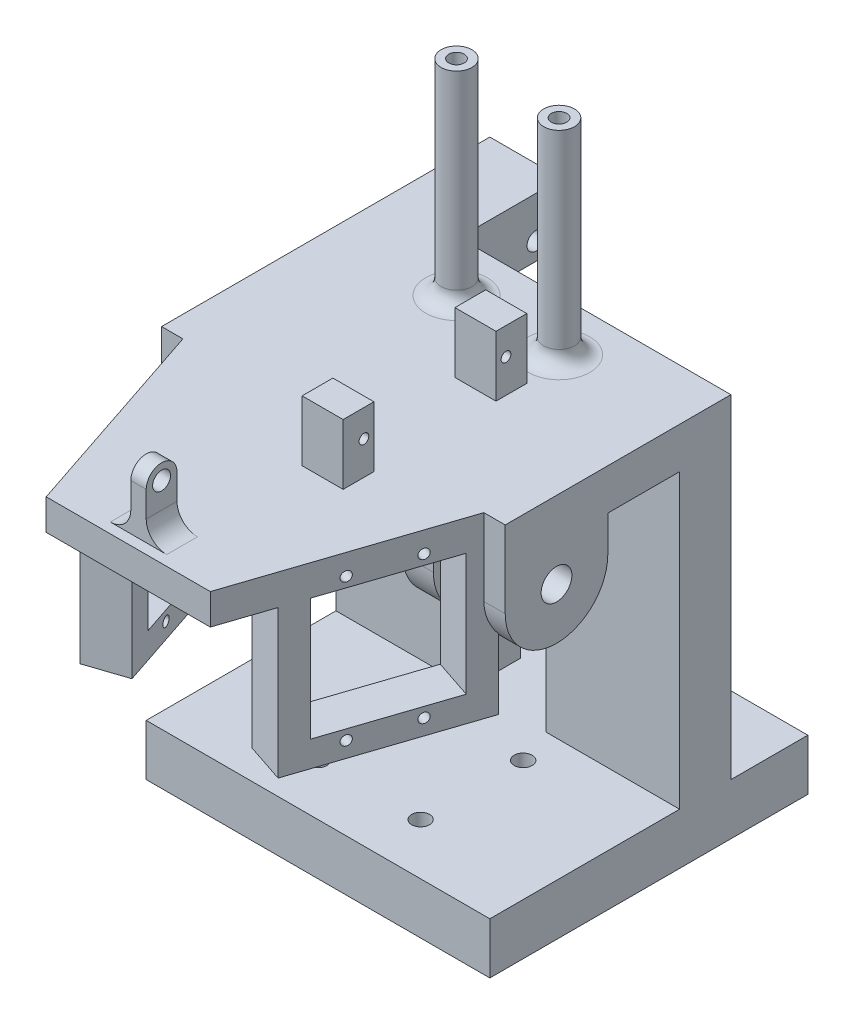
SolidWorks part; units mm, degrees
ref_plane "前视基准面" through (0, 0, 0) normal (0, 0, 1) x (1, 0, 0)
ref_plane "上视基准面" through (0, 0, 0) normal (0, 1, 0) x (1, 0, 0)
ref_plane "右视基准面" through (0, 0, 0) normal (1, 0, 0) x (0, 0, -1)
sketch "草图1" plane through (0, 0, 0) normal (0, 1, 0) x (1, 0, 0)
  line L1 (-33.5, 31) -> (33.5, 31)
  line L2 (-33.5, 31) -> (-33.5, -31)
  line L3 (-33.5, -31) -> (33.5, -31)
  line L4 (33.5, 31) -> (33.5, -31)
  line L5 (-33.5, 31) -> (33.5, -31) construction
  line L6 (-33.5, -31) -> (33.5, 31) construction
  point P0 (0, 0)
  dimension "D1" = 62
  dimension "D2" = 67
extrude "凸台-拉伸1" add sketch "草图1" along normal blind 10
sketch "草图3" plane through (0, 10, 0) normal (0, 1, 0) x (1, 0, 0)
  line L0 (-33.5, 31) -> (-33.5, -31) construction
  line L1 (-33.5, 36) -> (-19.5, 36)
  line L2 (-33.5, 36) -> (-33.5, 16)
  line L3 (-33.5, 16) -> (-19.5, 16)
  line L4 (-19.5, 36) -> (-19.5, 16)
  line L5 (33.5, 31) -> (-33.5, 31) construction
  dimension "D1" = 20
  dimension "D2" = 5
  dimension "D3" = 19.5
extrude "凸台-拉伸2" add sketch "草图3" along normal blind 12.5
sketch "草图4" plane through (-33.5, 0, 0) normal (-1, 0, 0) x (0, 0, 1)
  line L1 (-16, 10) -> (-6, 10)
  line L2 (-16, 10) -> (-16, 75)
  line L3 (-16, 75) -> (-6, 75)
  line L4 (-6, 10) -> (-6, 75)
  dimension "D1" = 10
  dimension "D2" = 65
extrude "凸台-拉伸3" add sketch "草图4" against normal blind 67
sketch "草图5" plane through (0, 75, 0) normal (0, 1, 0) x (1, 0, 0)
  line L0 (33.5, -31) -> (33.5, 6) construction
  line L1 (-33.5, 16) -> (33.5, 16)
  line L2 (-33.5, 16) -> (-33.5, -28)
  line L3 (-33.5, -28) -> (33.5, -28)
  line L4 (33.5, 16) -> (33.5, -28)
  dimension "D1" = 44
extrude "凸台-拉伸4" add sketch "草图5" against normal blind 8
sketch "草图6" plane through (33.5, 0, 0) normal (1, 0, 0) x (0, 0, -1)
  line L0 (6, 10) -> (6, 67) construction
  line L1 (-28, 75) -> (16, 75) construction
  line L2 (-28, 60) -> (-28, 67)
  line L3 (-28, 67) -> (6, 67) construction
  line L5 (-28, 67) -> (-8, 67)
  line L6 (-8, 67) -> (-8, 60)
  arc A0 (-28, 60) -> (-8, 60) centre (-18, 60) ccw
  dimension "D1" = 24
  dimension "D2" = 15
  dimension "D3" = 20
extrude "凸台-拉伸5" add sketch "草图6" against normal blind 20
sketch "草图7" plane through (33.5, 0, 0) normal (1, 0, 0) x (0, 0, -1)
  line L0 (-28, 60) -> (-28, 70.0002)
  line L1 (-28, 60) -> (-28, 75) construction
  line L2 (-28, 70.0002) -> (-8, 70.0002)
  line L3 (-8, 70.0002) -> (-8, 60)
  arc A0 (-28, 60) -> (-8, 60) centre (-18, 60) ccw construction
  arc A1 (-28, 60) -> (-8, 60) centre (-18, 60) ccw
extrude "切除-拉伸1" cut sketch "草图7" against normal blind 8 from offset 6 offset against normal yes
sketch "草图8" plane through (0, 75, 0) normal (0, 1, 0) x (1, 0, 0)
  line L0 (0, -68) -> (16, -68)
  line L2 (16, -68) -> (29.3377, -28)
  line L3 (29.3377, -28) -> (0, -28)
  line L4 (0, -28) -> (0, -68)
  line L5 (-33.5, -28) -> (33.5, -28) construction
  dimension "D1" = 16
  dimension "D2" = 40
extrude "凸台-拉伸6" add sketch "草图8" against normal blind 6
sketch "草图9" plane through (33.5, 0, 0) normal (1, 0, 0) x (0, 0, -1)
  circle A0 centre (-18, 60) radius 3
  dimension "D1" = 6
extrude "切除-拉伸2" cut sketch "草图9" against normal blind 23
sketch "草图10" plane through (34.8044, 0, 11.6052) normal (0.9487, 0, 0.3163) x (0.3163, 0, -0.9487)
  line L1 (-44, 75) -> (-15, 75)
  line L4 (-15, 75) -> (-15, 40.2)
  line L5 (-15, 40.2) -> (-43, 40.2)
  line L9 (-44, 45.2) -> (-20, 45.2)
  line L10 (-20, 45.2) -> (-20, 69)
  line L11 (-20, 69) -> (-44, 69)
  line L12 (-59.4472, 75) -> (-17.2822, 75) construction
  line L14 (-44, 75) -> (-49, 75)
  line L15 (-59.4472, 75) -> (-17.2822, 75) construction
  line L16 (-44, 69) -> (-44, 45.2)
  line L17 (-43, 40.2) -> (-49, 40.2)
  line L18 (-49, 75) -> (-49, 40.2)
  dimension "D1" = 5
  dimension "D2" = 5
  dimension "D3" = 29
  dimension "D4" = 15
  dimension "D5" = 24
  dimension "D6" = 28
  dimension "D7" = 5
  dimension "D8" = 6
  dimension "D9" = 23.8
extrude "凸台-拉伸7" add sketch "草图10" against normal blind 8
sketch "草图12" plane through (0, 75, 0) normal (0, 1, 0) x (1, 0, 0)
  line L1 (-33.5, 36) -> (-19.5, 36)
  line L2 (-33.5, 36) -> (-33.5, 16)
  line L3 (-33.5, 16) -> (-19.5, 16)
  line L4 (-19.5, 36) -> (-19.5, 16)
extrude "凸台-拉伸8" add sketch "草图12" against normal blind 11.5
sketch "草图13" plane through (27.2152, 0, 9.0747) normal (-0.9487, 0, -0.3163) x (-0.3163, 0, 0.9487)
  line L0 (59.4472, 69) -> (49, 69) construction
  line L7 (20, 69) -> (20, 45.2) construction
  line L8 (20, 45.2) -> (44, 45.2) construction
  circle A0 centre (38.5, 70.95) radius 0.95
  circle A1 centre (26.5, 70.95) radius 0.95
  circle A2 centre (26.5, 43.25) radius 0.95
  circle A3 centre (38.5, 43.25) radius 0.95
  dimension "D2" = 6.5
  dimension "D3" = 1.95
  dimension "D4" = 1.95
  dimension "D5" = 12
  dimension "D6" = 1.9
  dimension "D7" = 1.9
  dimension "D13" = 1.9
  dimension "D14" = 1.9
extrude "切除-拉伸4" cut sketch "草图13" against normal up to surface (8 mm away) up to face at (23.6536, 60.2504, 45.0468)
sketch "草图14" plane through (0, 75, 0) normal (0, 1, 0) x (1, 0, 0)
  line L0 (33.5, 6) -> (-33.5, 6) construction
  line L1 (3.7, -2) -> (11.7, -2)
  line L2 (3.7, -2) -> (3.7, -8)
  line L3 (3.7, -8) -> (11.7, -8)
  line L4 (11.7, -2) -> (11.7, -8)
  line L5 (11.7, -31.8) -> (11.7, -37.8)
  line L6 (3.7, -37.8) -> (11.7, -37.8)
  line L7 (3.7, -31.8) -> (3.7, -37.8)
  line L8 (3.7, -31.8) -> (11.7, -31.8)
  dimension "D1" = 11.7
  dimension "D2" = 3.7
  dimension "D3" = 6
  dimension "D4" = 14
  dimension "D5" = 6
  dimension "D6" = 8
  dimension "D7" = 23.8
extrude "凸台-拉伸9" add sketch "草图14" along normal blind 11.8
sketch "草图15" plane through (3.7, 0, 0) normal (-1, 0, 0) x (0, 0, 1)
  line L0 (8, 86.8) -> (8, 75) construction
  line L1 (28, 75) -> (-36, 75) construction
  line L2 (31.8, 75) -> (37.8, 75) construction
  line L3 (31.8, 86.8) -> (31.8, 75) construction
  circle A0 centre (33.75, 81.5) radius 0.95
  circle A1 centre (6.05, 81.5) radius 0.95
  dimension "D1" = 1.95
  dimension "D2" = 1.95
  dimension "D3" = 1.9
  dimension "D4" = 1.9
  dimension "D5" = 6.5
  dimension "D6" = 6.5
extrude "切除-拉伸5" cut sketch "草图15" against normal blind 11.8
sketch "草图16" plane through (0, 75, 0) normal (0, 1, 0) x (1, 0, 0)
  line L1 (-1.5, -60) -> (1.5, -60)
  line L2 (-1.5, -60) -> (-1.5, -66)
  line L3 (-1.5, -66) -> (1.5, -66)
  line L4 (1.5, -60) -> (1.5, -66)
  point P4 (0, -66)
  dimension "D2" = 6
  dimension "D3" = 3
  dimension "D4" = 60
extrude "凸台-拉伸10" add sketch "草图16" along normal blind 12
fillet "圆角1" 2 edges at (0, 87, 66) (0, 87, 60) type full round first side face at (0, 79.8, 66) second side face at (0, 79.8, 60) middle face at (0, 87, 63)
sketch "草图17" plane through (-1.5, 0, 0) normal (-1, 0, 0) x (0, 0, 1)
  circle A0 centre (63, 84) radius 1.75
  arc A1 (66, 84) -> (60, 84) centre (63, 84) ccw construction
  dimension "D1" = 3.5
extrude "切除-拉伸6" cut sketch "草图17" against normal blind 7
sketch "草图18" plane through (0, 75, 0) normal (0, 1, 0) x (1, 0, 0)
  line L0 (33.5, 16) -> (-19.5, 16) construction
  circle A0 centre (10, 6) radius 3
  dimension "D1" = 6
  dimension "D2" = 10
  dimension "D3" = 10
extrude "凸台-拉伸11" add sketch "草图18" along normal blind 40
fillet "圆角2" radius 3 1 edges at (10, 75, -3)
mirror "镜向1" about plane through (0, 0, 0) normal (1, 0, 0) of "圆角2", "凸台-拉伸11", "切除-拉伸4", "凸台-拉伸7", "切除-拉伸2", "凸台-拉伸6", "切除-拉伸1", "凸台-拉伸5"
sketch "草图20" plane through (-33.5, 0, 0) normal (-1, 0, 0) x (0, 0, 1)
  line L0 (-36, 63.5) -> (-16, 63.5) construction
  line L1 (-36, 63.5) -> (-36, 75) construction
  circle A0 centre (-31, 67) radius 1.75
  circle A1 centre (-21, 67) radius 1.75
  circle A2 centre (-31, 19) radius 1.75
  circle A3 centre (-21, 19) radius 1.75
  dimension "D1" = 3.5
  dimension "D2" = 10
  dimension "D3" = 48
  dimension "D4" = 3.5
  dimension "D5" = 5
extrude "切除-拉伸7" cut sketch "草图20" against normal blind 35
sketch "草图21" plane through (0, 0, -16) normal (0, 0, -1) x (-1, 0, 0)
  line L1 (-7.5, 65) -> (7.5, 65)
  line L2 (-7.5, 65) -> (-7.5, 10)
  line L3 (-7.5, 10) -> (7.5, 10)
  line L4 (7.5, 65) -> (7.5, 10)
  line L5 (-33.5, 10) -> (19.5, 10) construction
  point P8 (0, 10)
  dimension "D1" = 15
  dimension "D2" = 55
extrude "切除-拉伸8" cut sketch "草图21" against normal blind 35
sketch "草图24" plane through (0, 10, 0) normal (0, 1, 0) x (1, 0, 0)
  line L0 (-33.5, -31) -> (33.5, -31) construction
  circle A0 centre (-10, -21) radius 1.75
  circle A1 centre (10, -21) radius 1.75
  circle A2 centre (-10, -1) radius 1.75
  circle A3 centre (10, -1) radius 1.75
  point P10 (0, -31)
  dimension "D1" = 20
  dimension "D2" = 20
  dimension "D5" = 10
  dimension "D6" = 3.5
  dimension "D7" = 10
  dimension "D3" = 20
  dimension "D4" = 20
extrude "切除-拉伸11" cut sketch "草图24" against normal blind 18
sketch "草图25" plane through (0, 115, 0) normal (0, 1, 0) x (1, 0, 0)
  circle A0 centre (10, 6) radius 1.5
  circle A1 centre (-10, 6) radius 1.5
  dimension "D1" = 3
  dimension "D2" = 3
extrude "切除-拉伸12" cut sketch "草图25" against normal blind 10
fillet "圆角3" radius 4 2 edges at (-1.5, 75, 63) (1.5, 75, 63)
sketch "草图26" plane through (0, 69, 0) normal (0, -1, 0) x (1, 0, 0)
  line L0 (-16, 68) -> (16, 68) construction
  line L1 (-4.9, 63.82) -> (4.9, 63.82)
  line L2 (-4.9, 63.82) -> (-4.9, 60.22)
  line L3 (-4.9, 60.22) -> (4.9, 60.22)
  line L4 (4.9, 63.82) -> (4.9, 60.22)
  line L5 (-4.9, 63.82) -> (4.9, 60.22) construction
  line L6 (-4.9, 60.22) -> (4.9, 63.82) construction
  line L7 (-33.5, -31) -> (-33.5, 31) construction
  point P0 (0, 62.02)
  dimension "D1" = 3.6
  dimension "D2" = 9.8
  dimension "D3" = 4.18
  dimension "D4" = 28.6
extrude "凸台-拉伸12" add sketch "草图26" along normal blind 1
sketch "草图27" plane through (0, 68, 0) normal (0, -1, 0) x (1, 0, 0)
  line L0 (-16, 68) -> (16, 68) construction
  line L1 (-33.5, -31) -> (-33.5, 31) construction
  circle A0 centre (0, 62) radius 1.4
  dimension "D1" = 2.8
  dimension "D2" = 6
  dimension "D3" = 33.5
extrude "切除-拉伸13" cut sketch "草图27" against normal blind 4
